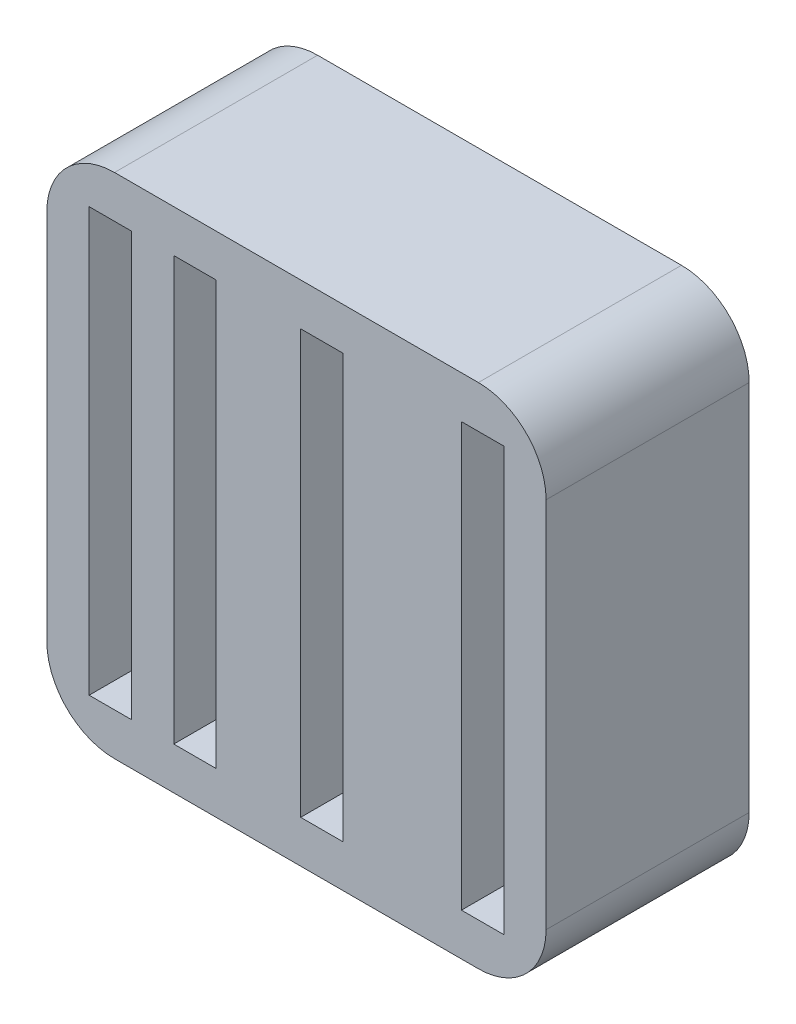
SolidWorks part; units mm, degrees
ref_plane "Front Plane" through (0, 0, 0) normal (0, 0, 1) x (1, 0, 0)
ref_plane "Top Plane" through (0, 0, 0) normal (0, 1, 0) x (1, 0, 0)
ref_plane "Right Plane" through (0, 0, 0) normal (1, 0, 0) x (0, 0, -1)
sketch "Sketch1" plane through (0, 0, 0) normal (0, 0, 1) x (1, 0, 0)
  line L0 (-10.472, 8.2019) -> (-7.972, 5.7019)
  line L1 (-10.472, 8.2019) -> (19.028, 8.2019)
  line L2 (-10.472, 8.2019) -> (-10.472, -21.7981)
  line L3 (-10.472, -21.7981) -> (19.028, -21.7981)
  line L4 (19.028, 8.2019) -> (19.028, -21.7981)
  line L5 (-7.972, 5.7019) -> (-5.472, 5.7019)
  line L6 (-7.972, 5.7019) -> (-7.972, -19.2981)
  line L7 (-7.972, -19.2981) -> (-5.472, -19.2981)
  line L8 (-5.472, 5.7019) -> (-5.472, -19.2981)
  line L9 (-7.972, -19.2981) -> (-10.472, -21.7981)
  line L10 (-7.972, 5.7019) -> (-10.472, 5.7019)
  line L11 (-2.972, 5.7019) -> (-0.472, 5.7019)
  line L12 (-2.972, 5.7019) -> (-2.972, -19.2981)
  line L13 (-2.972, -19.2981) -> (-0.472, -19.2981)
  line L14 (-0.472, 5.7019) -> (-0.472, -19.2981)
  line L15 (4.528, -19.2981) -> (7.028, -19.2981)
  line L16 (4.528, -19.2981) -> (4.528, 5.7019)
  line L17 (4.528, 5.7019) -> (7.028, 5.7019)
  line L18 (7.028, -19.2981) -> (7.028, 5.7019)
  line L19 (-5.472, 5.7019) -> (-2.972, 5.7019)
  line L20 (-0.472, 5.7019) -> (4.528, 5.7019)
  line L21 (7.028, 5.7019) -> (14.028, 5.7019)
  line L22 (16.528, 5.7019) -> (19.028, 5.7019)
  line L23 (14.028, 5.7019) -> (16.528, 5.7019)
  line L24 (14.028, 5.7019) -> (14.028, -19.2981)
  line L25 (14.028, -19.2981) -> (16.528, -19.2981)
  line L26 (16.528, 5.7019) -> (16.528, -19.2981)
  dimension "D1" = 2.5
  dimension "D2" = 25
  dimension "D3" = 30
  dimension "D4" = 2.5
  dimension "D5" = 2.5
  dimension "D6" = 2.5
  dimension "D7" = 5
  dimension "D8" = 2.5
  dimension "D9" = 2.5
  dimension "D10" = 2.5
  dimension "D11" = 7
  dimension "D12" = 2.5
  dimension "D13" = 25
  dimension "D14" = 25
  dimension "D15" = 25
extrude "Boss-Extrude3" add sketch "Sketch1" along normal blind 2 contours L21 L23 L22 L4 L1 L0 L5 L19 L11 L20 L17 | L6 L10 L2 L9 | L10 L0 L2 | L22 L26 L25 L24 L21 L18 L15 L16 L20 L14 L13 L12 L19 L8 L7 L9 L3 L4 | L15 L18 L17 L16 | L26 L23 L24 L25 | L14 L11 L12 L13 | L8 L5 L6 L7 region at (4.8937, 6.9703, 0) region at (-9.6387, 6.5352, 0) region at (-6.722, -6.7981, 0) region at (-9.2419, -7.4331, 0) region at (-4.222, 5.2986, 0) region at (-1.722, -6.7981, 0) region at (15.278, -6.7981, 0) region at (5.778, -6.7981, 0)
extrude "Boss-Extrude4" add sketch "Sketch1<8>" along normal blind 12 contours L22 L26 L25 L24 L21 L18 L15 L16 L20 L14 L13 L12 L19 L8 L7 L9 L3 L4 | L21 L23 L22 L4 L1 L0 L5 L19 L11 L20 L17 | L6 L10 L2 L9 | L10 L0 L2 region at (4.8937, 6.9703, 0) region at (-9.6387, 6.5352, 0) region at (-9.2419, -7.4331, 0) region at (-4.222, 5.2986, 0)
sketch "Sketch1<8>" plane through (0, 0, 0) normal (0, 0, 1) x (1, 0, 0) same geometry as "Sketch1"
fillet "Fillet2" radius 4 4 edges at (19.028, -21.7981, 6) (-10.472, -21.7981, 6) (-10.472, 8.2019, 6) (19.028, 8.2019, 6)
